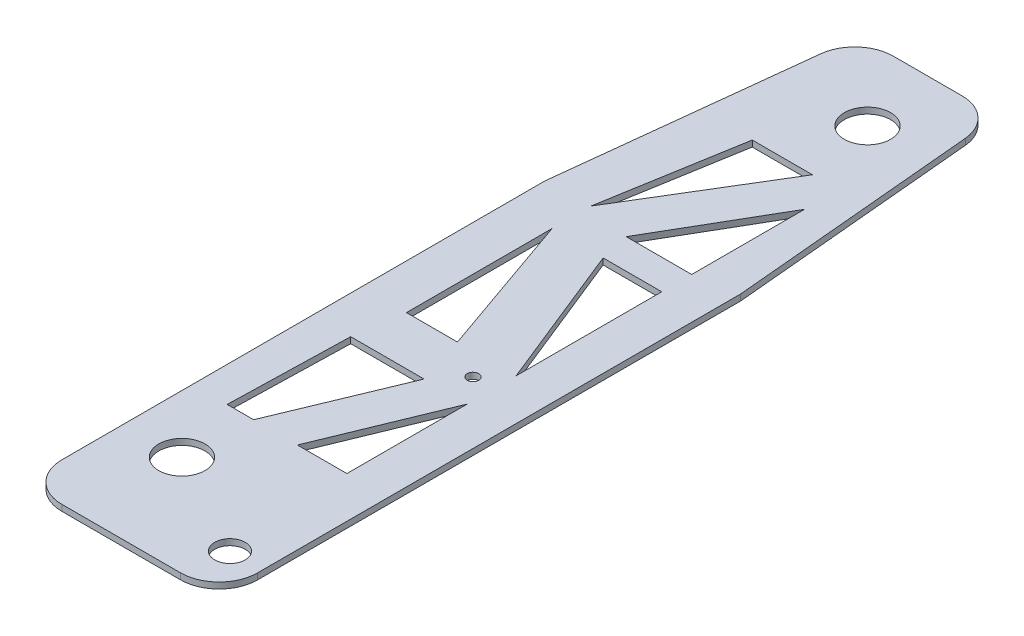
SolidWorks part; units mm, degrees
ref_plane "Front" through (0, 0, 0) normal (0, 0, 1) x (1, 0, 0)
ref_plane "Top" through (0, 0, 0) normal (0, 1, 0) x (1, 0, 0)
ref_plane "Right" through (0, 0, 0) normal (1, 0, 0) x (0, 0, -1)
sketch "Sketch1" plane through (0, 0, 0) normal (0, 1, 0) x (1, 0, 0)
  line L0 (10.4543, 228.6) -> (0, 135.3627)
  line L1 (0, 0) -> (50.8, 0)
  line L2 (0, 0) -> (0, 228.6)
  line L3 (0, 228.6) -> (50.8, 228.6)
  line L4 (50.8, 0) -> (50.8, 228.6)
  line L5 (42.3273, 228.6) -> (50.8, 135.3627)
  line L8 (50.8, 0) -> (24.327, 0)
  line L9 (50.8, 0) -> (50.8, -15)
  line L10 (50.8, -15) -> (24.327, -15)
  line L11 (24.327, 0) -> (24.327, -15)
  circle A0 centre (29.5042, 189.5572) radius 6
  circle A2 centre (24.327, 25.5092) radius 5.969
  circle A3 centre (42.3273, 11.2956) radius 3.9601
  dimension "D3" = 12
  dimension "D4" = 11.938
  dimension "D5" = 15
  dimension "D1" = 50.8
  dimension "D2" = 228.6
extrude "Boss-Extrude1" add sketch "Sketch1" along normal blind 1.5875 contours L1 L4 L3 L0 L2 region at (25.456, 0, -107.8992)
fillet "Fillet1" radius 10 4 edges at (0, 0.7937, -135.3627) (10.4543, 0.7937, -228.6) (50.8, 0.7937, 0) (0, 0.7937, 0)
sketch "Sketch2" plane through (0, 1.5875, 0) normal (0, 1, 0) x (1, 0, 0)
  line L0 (17.7103, 171.4473) -> (11.6259, 135.6828)
  line L3 (17.7103, 171.4473) -> (33.327, 171.4473)
  line L4 (33.327, 171.4473) -> (11.6259, 135.6828)
  line L5 (40.07, 162.6734) -> (40.07, 137.6523)
  line L8 (40.07, 162.6734) -> (23.0737, 133.3724)
  line L9 (23.0737, 133.3724) -> (40.07, 133.3724)
  line L10 (40.07, 133.3724) -> (40.07, 137.6523)
  line L11 (11.6259, 125.5961) -> (11.6259, 87.7975)
  line L12 (11.6259, 87.7975) -> (24.8595, 87.7975)
  line L13 (24.8595, 87.7975) -> (11.6259, 125.5961)
  line L14 (24.8595, 125.5961) -> (40.07, 125.5961)
  line L15 (40.07, 125.5961) -> (40.07, 87.7975)
  line L16 (40.07, 87.7975) -> (24.8595, 125.5961)
  line L20 (28.8434, 75.1474) -> (9.809, 75.1474)
  line L23 (40.07, 75.1474) -> (40.07, 43.8914)
  line L24 (40.07, 43.8914) -> (31.2784, 43.8914)
  line L26 (40.07, 75.1474) -> (27.2385, 43.8914)
  line L27 (27.2385, 43.8914) -> (31.2784, 43.8914)
  line L28 (9.809, 75.1474) -> (9.002, 43.8914)
  line L30 (28.8434, 75.1474) -> (15.8732, 43.8914)
  line L31 (15.8732, 43.8914) -> (9.002, 43.8914)
extrude "Cut-Extrude1" cut sketch "Sketch2" against normal blind 10
sketch "Sketch4" plane through (0, 0, -228.6) normal (0, 0, -1) x (-1, 0, 0)
  line L1 (-61.3109, 11.9192) -> (4.9615, 11.9192)
  line L2 (-61.3109, 11.9192) -> (-61.3109, -15.8811)
  line L3 (-61.3109, -15.8811) -> (4.9615, -15.8811)
  line L4 (4.9615, 11.9192) -> (4.9615, -15.8811)
extrude "Cut-Extrude2" cut sketch "Sketch4" against normal blind 20
fillet "Fillet2" radius 10 1 edges at (8.2118, 0.7937, -208.6)
sketch "Sketch5" plane through (0, 0, 0) normal (0, -1, 0) x (1, 0, 0)
  circle A0 centre (24.327, -25.5092) radius 6.6837
extrude "Boss-Extrude2" add sketch "Sketch5" against normal blind 1.5875
sketch "Sketch6" plane through (0, 0, 0) normal (0, -1, 0) x (1, 0, 0)
  line L0 (0, -10) -> (0, -134.8039) construction
  circle A0 centre (15, -26.1497) radius 6
  circle A1 centre (29.5042, -189.5572) radius 6 construction
  dimension "D1" = 164.05
  dimension "D2" = 12
  dimension "D3" = 15
extrude "Cut-Extrude3" cut sketch "Sketch6" against normal blind 2
fillet "Fillet3" radius 10 1 edges at (44.1447, 0.7937, -208.6)
sketch "Sketch7" plane through (0, 0, 0) normal (0, -1, 0) x (1, 0, 0)
  circle A0 centre (34.714, -81.9581) radius 1.5
extrude "Cut-Extrude4" cut sketch "Sketch7" against normal blind 3.175
equation "\"7i\"=101.6"
